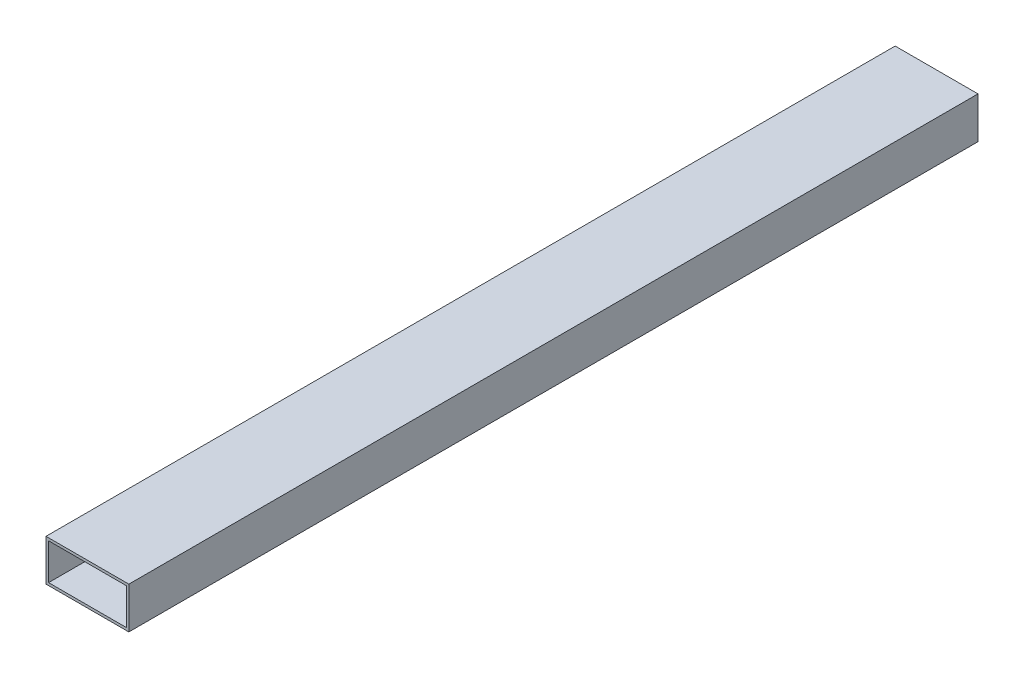
SolidWorks part; units mm, degrees
ref_plane "Front Plane" through (0, 0, 0) normal (0, 0, 1) x (1, 0, 0)
ref_plane "Top Plane" through (0, 0, 0) normal (0, 1, 0) x (1, 0, 0)
ref_plane "Right Plane" through (0, 0, 0) normal (1, 0, 0) x (0, 0, -1)
sketch "Sketch1" plane through (0, 0, 0) normal (0, 0, 1) x (1, 0, 0)
  line L0 (-23.8125, 11.1125) -> (23.8125, 11.1125)
  line L2 (-25.4, 12.7) -> (25.4, 12.7)
  line L3 (-25.4, 12.7) -> (-25.4, -12.7)
  line L4 (-25.4, -12.7) -> (25.4, -12.7)
  line L5 (25.4, 12.7) -> (25.4, -12.7)
  line L10 (23.8125, 11.1125) -> (23.8125, -11.1125)
  line L11 (-23.8125, -11.1125) -> (23.8125, -11.1125)
  line L12 (-23.8125, 11.1125) -> (-23.8125, -11.1125)
  point P12 (0, 12.7)
  point P14 (25.4, 0)
  dimension "Wall Thickness" = 1.5875
  dimension "Outside Width" = 50.8
  dimension "Outside Height" = 25.4
  dimension "Inside Height" = 22.225
  dimension "Inside Width" = 47.625
sketch "Sketch2" plane through (0, 0, 0) normal (1, 0, 0) x (0, 0, -1)
  line L0 (260.35, 0) -> (-260.35, 0)
  point P4 (0, 0)
  point P7 (-260.35, 0)
  point P10 (260.35, 0)
  dimension "Length" = 520.7
sketch "Sketch3" plane through (0, 0, 0) normal (0, 0, 1) x (1, 0, 0)
  line L21 (25.4, 12.7) -> (-25.4, 12.7)
  line L22 (25.4, -12.7) -> (25.4, 12.7)
  line L23 (-25.4, -12.7) -> (25.4, -12.7)
  line L24 (-25.4, 12.7) -> (-25.4, -12.7)
  line L25 (25.4, 12.7) -> (-25.4, 12.7)
  line L26 (25.4, -12.7) -> (25.4, 12.7)
  line L27 (-25.4, -12.7) -> (25.4, -12.7)
  line L28 (-25.4, 12.7) -> (-25.4, -12.7)
  line L29 (23.8125, 11.1125) -> (-23.8125, 11.1125)
  line L30 (23.8125, -11.1125) -> (23.8125, 11.1125)
  line L31 (-23.8125, -11.1125) -> (23.8125, -11.1125)
  line L32 (-23.8125, 11.1125) -> (-23.8125, -11.1125)
  line L33 (23.8125, 11.1125) -> (-23.8125, 11.1125)
  line L34 (23.8125, -11.1125) -> (23.8125, 11.1125)
  line L35 (-23.8125, -11.1125) -> (23.8125, -11.1125)
  line L36 (-23.8125, 11.1125) -> (-23.8125, -11.1125)
  dimension "D1" = 0
  dimension "D2" = 0
extrude "Boss-Extrude1" add sketch "Sketch3" along normal up to vertex (260.35 mm away) and the other way up to vertex (260.35 mm away) up to point (0, 0, 260.35) other way up to point (0, 0, -260.35)
sketch "Drawing Reference" plane through (0, 0, 0) normal (1, 0, 0) x (0, 0, -1)
  line L0 (-260.35, 0) -> (260.35, 0) construction
  line L1 (0, -12.7) -> (0, 12.7) construction
  line L2 (-260.35, -12.7) -> (260.35, -12.7) construction
  line L5 (-260.35, 12.7) -> (260.35, 12.7) construction
  point P7 (-223.774, 0)
  point P8 (223.774, 0)
  dimension "D1" = 36.576
equation "\"D1@Drawing Reference\"=\"Outside Width@Sketch1\" * 0.72"
